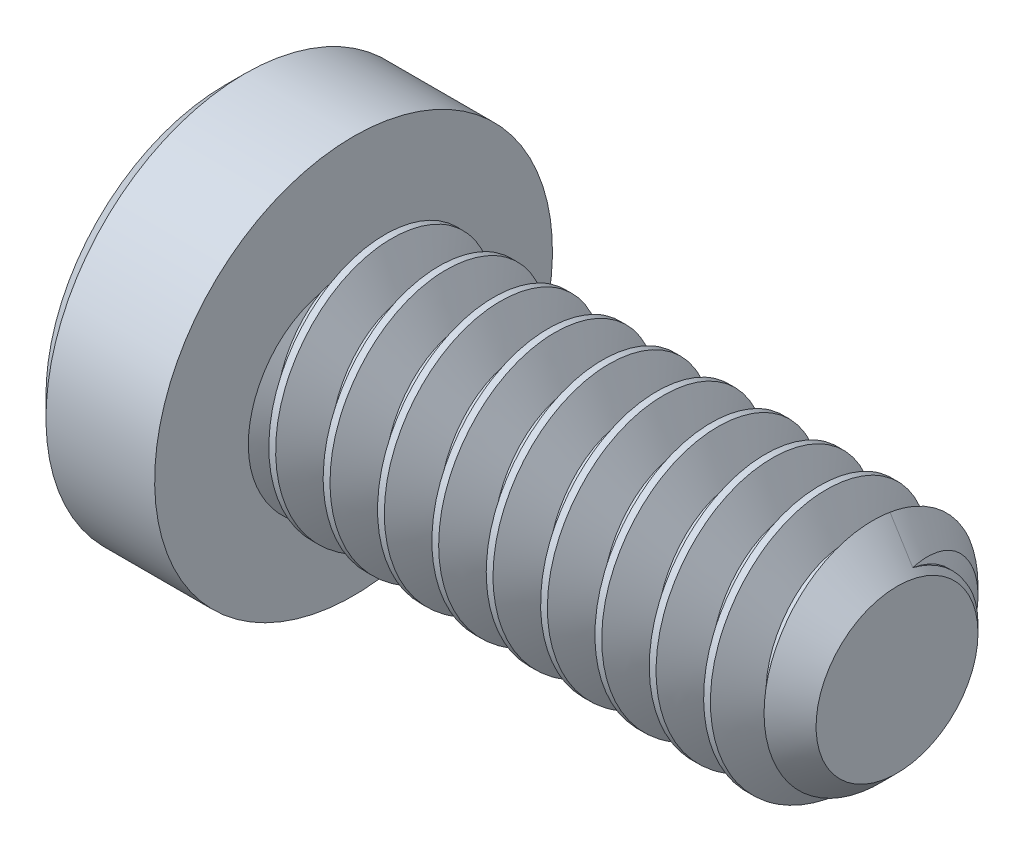
SolidWorks part; units mm, degrees
ref_plane "Front Plane" through (0, 0, 0) normal (0, 0, 1) x (1, 0, 0)
ref_plane "Top Plane" through (0, 0, 0) normal (0, 1, 0) x (1, 0, 0)
ref_plane "Right Plane" through (0, 0, 0) normal (1, 0, 0) x (0, 0, -1)
sketch "Sketch1" plane through (0, 0, 0) normal (0, 0, 1) x (1, 0, 0)
  line L0 (3.175, 0) -> (-3.175, 0) construction
  line L1 (3.175, 1.4224) -> (3.175, -1.4224) construction
  line L2 (-3.175, 2.3241) -> (-3.175, -2.3241) construction
  line L3 (-3.175, 2.3241) -> (-4.445, 2.3241) construction
  line L4 (-4.445, 2.3241) -> (-4.6736, 2.0955) construction
  line L5 (-4.6736, 2.0955) -> (-4.6736, -2.0955) construction
  line L6 (-4.6736, -2.0955) -> (-4.445, -2.3241) construction
  line L7 (-4.445, -2.3241) -> (-3.175, -2.3241) construction
  point P7 (-3.7084, 0)
  point P12 (0.635, -1.4224)
  dimension "D1" = 45
  dimension "Dec." = 2.8448
  dimension "Length" = 6.35
  dimension "Head Dia" = 4.6482
  dimension "Head Height" = 1.4986
  dimension "Hex Depth" = 0.9652
  dimension "Chamfer" = 0.2286
  dimension "D2" = 2.54
ref_plane "Plane1" through (3.175, 0, 0) normal (1, 0, 0) x (0, 0, -1)
ref_plane "Plane2" through (-4.6736, 0, 0) normal (1, 0, 0) x (0, 0, -1)
sketch "Sketch2" plane through (3.175, 0, 0) normal (1, 0, 0) x (0, 0, -1)
  circle A0 centre (0, 0) radius 1.4224
extrude "Boss-Extrude1" add sketch "Sketch2" against normal up to vertex (6.35 mm away) up to point (-3.175, 0, 0)
sketch "Sketch3" plane through (3.175, 0, 0) normal (1, 0, 0) x (0, 0, -1)
  circle A0 centre (0, 0) radius 1.4224 construction
  circle A1 centre (0, 0) radius 1.4224
curve "Helix/Spiral1" pitch 0.635 height 6.985 radius 1.4224 centre (3.175, 0, 0) axis (-1, 0, 0) start towards (0, 1, 0) parameters "Pitch"=0.635
chamfer "Chamfer1" distance 0.4763 angle 45 1 edges at (3.175, 0, -1.4224)
sketch "Sketch5" plane through (0, 0, 0) normal (0, 0, 1) x (1, 0, 0)
  line L0 (2.8972, 1.4224) -> (3.4528, 1.4224)
  line L1 (3.4528, 1.4224) -> (3.2147, 1.01)
  line L2 (3.2147, 1.01) -> (3.1353, 1.01)
  line L3 (3.1353, 1.01) -> (2.8972, 1.4224)
  line L4 (3.175, 1.01) -> (3.175, 1.4224) construction
  line L5 (3.0162, 1.2162) -> (3.3337, 1.2162) construction
  dimension "D1" = 60
  dimension "D2" = 0.3175
  dimension "D3" = 0.0794
sweep "Cut-Sweep1" cut profiles "Sketch5" path "Helix/Spiral1" align with end faces yes
sketch "Sketch4" plane through (-4.6736, 0, 0) normal (1, 0, 0) x (0, 0, -1)
  line L0 (-2.3241, 0.7937) -> (2.3241, 0.7937) construction
  line L1 (0, 0.7332) -> (-0.635, 0.3666)
  line L2 (-0.635, 0.3666) -> (-0.635, -0.3666)
  line L3 (-0.635, -0.3666) -> (0, -0.7332)
  line L4 (0, -0.7332) -> (0.635, -0.3666)
  line L5 (0.635, -0.3666) -> (0.635, 0.3666)
  line L6 (0.635, 0.3666) -> (0, 0.7332)
  line L7 (0, 0) -> (0, 0.7937) construction
  circle A0 centre (0, 0) radius 0.635 construction
  dimension "Hex Size" = 1.27
  dimension "D1" = 4.6482
  dimension "D2" = 0.7937
sketch "Sketch6" plane through (0, 0, 0) normal (0, 0, 1) x (1, 0, 0)
  line L0 (-4.445, 2.3241) -> (-4.6736, 2.0955) construction
  line L1 (-3.175, 2.3241) -> (-4.445, 2.3241) construction
  line L2 (-3.175, 2.3241) -> (-3.175, -2.3241) construction
  line L3 (-4.6736, 2.0955) -> (-4.6736, -2.0955) construction
  line L4 (-4.445, 2.3241) -> (-4.6736, 2.0955)
  line L5 (-3.175, 2.3241) -> (-4.445, 2.3241)
  line L6 (-3.175, 2.3241) -> (-3.175, 0)
  line L7 (-4.6736, 2.0955) -> (-4.6736, 0)
  line L8 (-3.175, 0) -> (-4.6736, 0) construction
  line L9 (-3.175, 0) -> (-4.6736, 0)
revolve "Revolve1" add sketch "Sketch6" angle 360 about L8
extrude "Cut-Extrude1" cut sketch "Sketch4" along normal up to vertex (0.9652 mm away) up to point (-3.7084, 0, 0)
sketch "Sketch8" plane through (-4.6736, 0, 0) normal (-1, 0, 0) x (0, 0, 1)
  circle A1 centre (0, 0) radius 0.7332
extrude "Cut-Extrude2" cut sketch "Sketch8" against normal through all draft 45
equation "\"D3@Helix/Spiral1\" = \"Length@Sketch1\"+\"Pitch@Helix/Spiral1\""
equation "\"D3@Sketch5\" = \"Pitch@Helix/Spiral1\"*.125"
equation "\"D2@Sketch5\" = \"Pitch@Helix/Spiral1\"*.50"
equation "\"D1@Chamfer1\" = \"Pitch@Helix/Spiral1\"*.75"
equation "\"D2@Sketch1\" = \"Pitch@Helix/Spiral1\"*4"
equation "\"D1@Sketch4\" = \"Head Dia@Sketch1\""
